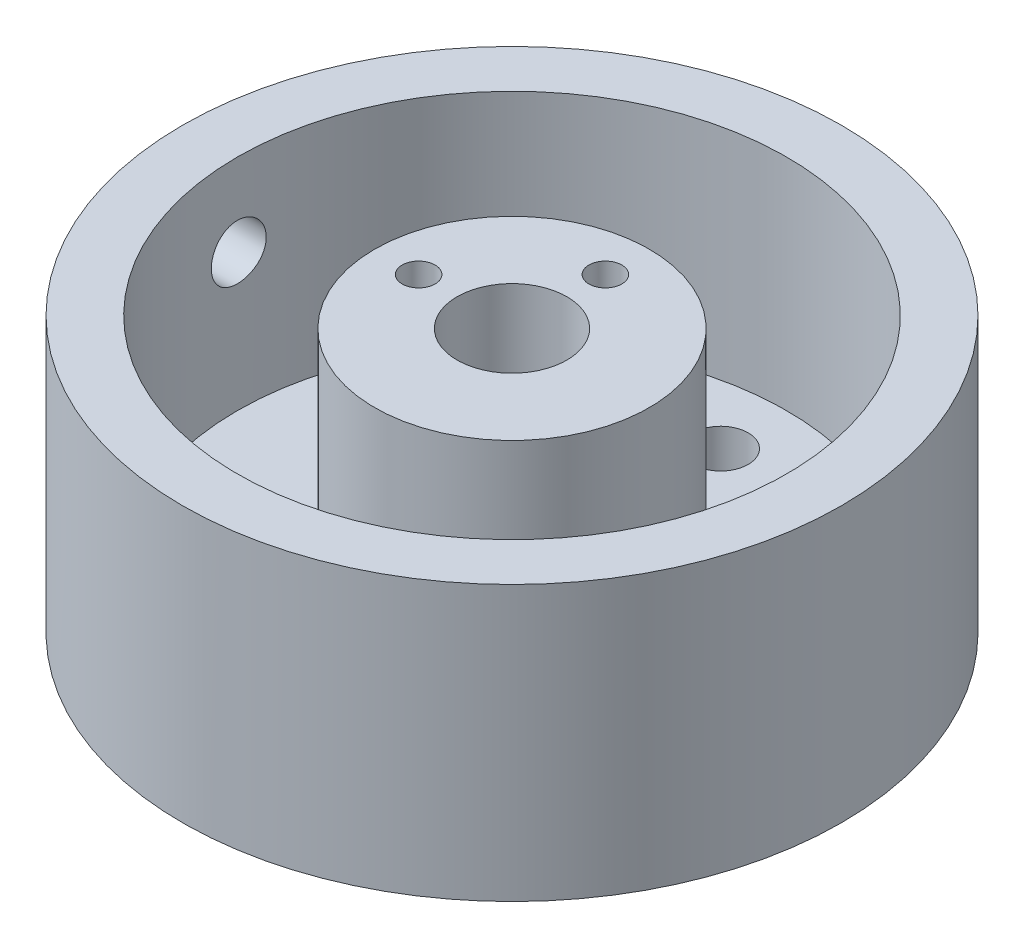
SolidWorks part; units mm, degrees
ref_plane "Front Plane" through (0, 0, 0) normal (0, 0, 1) x (1, 0, 0)
ref_plane "Top Plane" through (0, 0, 0) normal (0, 1, 0) x (1, 0, 0)
ref_plane "Right Plane" through (0, 0, 0) normal (1, 0, 0) x (0, 0, -1)
sketch "Sketch1" plane through (0, 0, 0) normal (0, 0, 1) x (1, 0, 0)
  line L0 (0, 23.98) -> (0, 0) construction
  line L1 (0, 0) -> (30, 0)
  line L2 (30, 0) -> (30, 25)
  line L3 (30, 25) -> (25, 25)
  line L4 (25, 25) -> (25, 5)
  line L5 (25, 5) -> (12.5, 5)
  line L6 (12.5, 5) -> (12.5, 23.98)
  line L7 (12.5, 23.98) -> (0, 23.98)
  line L8 (5, 23.98) -> (5, 0)
  line L9 (5, 11.48) -> (7, 11.48)
  line L10 (7, 11.48) -> (7, 7.28)
  line L11 (7, 7.28) -> (5, 7.28)
  dimension "D1" = 30
  dimension "D2" = 25
  dimension "D3" = 5
  dimension "D4" = 5
  dimension "D5" = 23.98
  dimension "D6" = 12.5
  dimension "D7" = 5
  dimension "D8" = 2
  dimension "D9" = 4.2
  dimension "D10" = 12.5
revolve "Revolve2" add sketch "Sketch1" angle 360 about L0 region at (5.3536, 3.64, 0)
sketch "Sketch2" plane through (0, 0, 0) normal (0, -1, 0) x (1, 0, 0)
  circle A0 centre (0, -19) radius 2.5
  dimension "D1" = 19
  dimension "D3" = 5
extrude "Cut-Extrude1" cut sketch "Sketch2" against normal blind 10
sketch "Sketch3" plane through (0, 23.98, 0) normal (0, 1, 0) x (1, 0, 0)
  circle A0 centre (-8.5, 0) radius 1.5
  circle A1 centre (0, 8.5) radius 1.5
  dimension "D1" = 3
  dimension "D2" = 8.5
  dimension "D3" = 8.5
extrude "Cut-Extrude2" cut sketch "Sketch3" against normal blind 8
ref_plane "Plane1" through (0, 0, -12.5) normal (0, 0, 1) x (1, 0, 0)
sketch "Sketch4" plane through (0, 0, -12.5) normal (0, 0, 1) x (1, 0, 0)
  line L0 (12.5, 23.98) -> (-12.5, 23.98) construction
  circle A0 centre (0, 17.5) radius 1.5
  dimension "D1" = 3
  dimension "D2" = 6.48
extrude "Cut-Extrude3" cut sketch "Sketch4" along normal blind 4
ref_plane "Plane2" through (-12.5, 0, 0) normal (1, 0, 0) x (0, 0, -1)
sketch "Sketch5" plane through (-12.5, 0, 0) normal (1, 0, 0) x (0, 0, -1)
  line L0 (5, 23.98) -> (-5, 23.98) construction
  circle A0 centre (0, 17.5) radius 1.5
  dimension "D1" = 6.48
  dimension "D2" = 3
extrude "Cut-Extrude4" cut sketch "Sketch5" along normal blind 4
ref_plane "Plane3" through (-30, 0, 0) normal (1, 0, 0) x (0, 0, -1)
sketch "Sketch6" plane through (-30, 0, 0) normal (1, 0, 0) x (0, 0, -1)
  circle A0 centre (0, 17.5) radius 2.5
  dimension "D1" = 5
extrude "Cut-Extrude7" cut sketch "Sketch6" along normal blind 10 and the other way blind 10
sketch "Sketch7" plane through (0, 0, 0) normal (0, 0, 1) x (1, 0, 0)
  line L0 (-32, 0) -> (-30, 0)
  line L1 (-30, 0) -> (30, 0) construction
  line L2 (-30, 0) -> (-15, 0)
  line L3 (-5, 0) -> (5, 0) construction
  line L4 (-15, 0) -> (-15, -9.5)
  line L5 (-18, -12.5) -> (-32, -12.5)
  line L6 (-35, -9.5) -> (-35, -3)
  arc A1 (-15, -9.5) -> (-18, -12.5) centre (-18, -9.5) cw
  arc A2 (-32, -12.5) -> (-35, -9.5) centre (-32, -9.5) cw
  arc A3 (-35, -3) -> (-32, 0) centre (-32, -3) cw
  point P3 (-15, -12.5)
  dimension "D1" = 30
  dimension "D8" = 3
  dimension "D5" = 12.5
extrude "Boss-Extrude5" add sketch "Sketch7" along normal blind 5 and the other way blind 5
sketch "Sketch8" plane through (0, 0, -5) normal (0, 0, -1) x (-1, 0, 0)
  point P5 (25, -8)
hole_wizard "Ø5.0 (5) Diameter Hole1" positions "3DSketch1" profile "Sketch9" hole size "Ø5.0" standard "DIN" end condition through all
sketch3d "3DSketch1"
  point P0 (-25, -8, -5)
  point P3 (-19.5551, -17.555, 0)
sketch "Sketch9" plane through (-25, -8, -5) normal (1, 0, 0) x (0, 1, 0)
  line L0 (0, 0) -> (0, 35)
  line L1 (0, 35) -> (2.5, 35)
  line L2 (2.5, 35) -> (2.5, 0)
  line L5 (2.5, 0) -> (0, 0)
  line L11 (0, -6.35) -> (0, 107.95) construction
  dimension "Thru Hole Dia." = 5
  dimension "Thru Hole Depth" = 35
